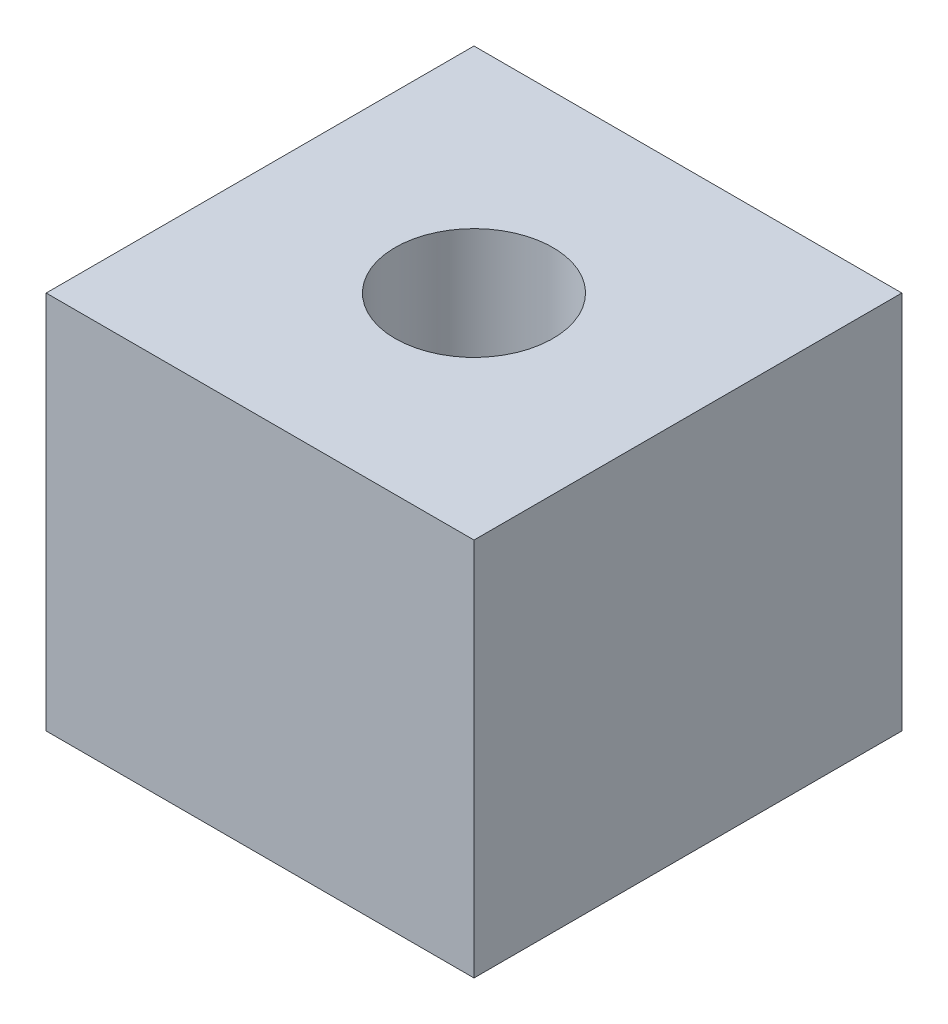
SolidWorks part; units mm, degrees
ref_plane "Front Plane" through (0, 0, 0) normal (0, 0, 1) x (1, 0, 0)
ref_plane "Top Plane" through (0, 0, 0) normal (0, 1, 0) x (1, 0, 0)
ref_plane "Right Plane" through (0, 0, 0) normal (1, 0, 0) x (0, 0, -1)
sketch "Sketch1" plane through (0, 0, 0) normal (0, 1, 0) x (1, 0, 0)
  line L0 (14.1, 14.1) -> (14.1, -14.1)
  line L7 (-14.1, -14.1) -> (14.1, -14.1)
  line L8 (-14.1, 14.1) -> (-14.1, -14.1)
  line L9 (-14.1, 14.1) -> (14.1, 14.1)
  circle A0 centre (8, 0) radius 1.5
  circle A1 centre (0, -8) radius 1.5
  circle A2 centre (-8, 0) radius 1.5
  circle A3 centre (0, 8) radius 1.5
  circle A6 centre (0, 0) radius 5.2
  circle A7 centre (0, 0) radius 11.1
extrude "Boss-Extrude1" add sketch "Sketch1" along normal blind 25 contours L9 L8 L7 L0 A7 | A7 A0 A1 A2 A3 A6 | A3 | A0 | A1 | A2 | A6 region at (13.7012, 0, 0) region at (8, 0, 0) region at (0, 0, 8) region at (-8, 0, 0) region at (0, 0, -8) region at (0, 0, 0) region at (-10.786, 0, 0)
extrude "Cut-Extrude1" cut sketch "Sketch1<4>" along normal blind 25 contours A6 region at (0, 0, 0)
sketch "Sketch1<4>" plane through (0, 0, 0) normal (0, 1, 0) x (1, 0, 0) same geometry as "Sketch1"
extrude "Cut-Extrude2" cut sketch "Sketch1<5>" along normal blind 8 contours A2 | A1 | A0 | A3 region at (8, 0, 0) region at (0, 0, 8) region at (-8, 0, 0) region at (0, 0, -8)
sketch "Sketch1<5>" plane through (0, 0, 0) normal (0, 1, 0) x (1, 0, 0) same geometry as "Sketch1"
extrude "Cut-Extrude3" cut sketch "Sketch1<6>" along normal blind 3.5 contours A7 A0 A1 A2 A3 A6 region at (-10.786, 0, 0)
sketch "Sketch1<6>" plane through (0, 0, 0) normal (0, 1, 0) x (1, 0, 0) same geometry as "Sketch1"
sketch "Sketch2" plane through (-14.1, 0, 0) normal (-1, 0, 0) x (0, 0, 1)
  circle A1 centre (-7.5, 20.5) radius 1.5
  circle A2 centre (7.5, 20.5) radius 1.5
  circle A3 centre (7.5, 4.5) radius 1.5
  circle A4 centre (-7.5, 4.5) radius 1.5
extrude "Cut-Extrude4" cut sketch "Sketch2" against normal blind 5
